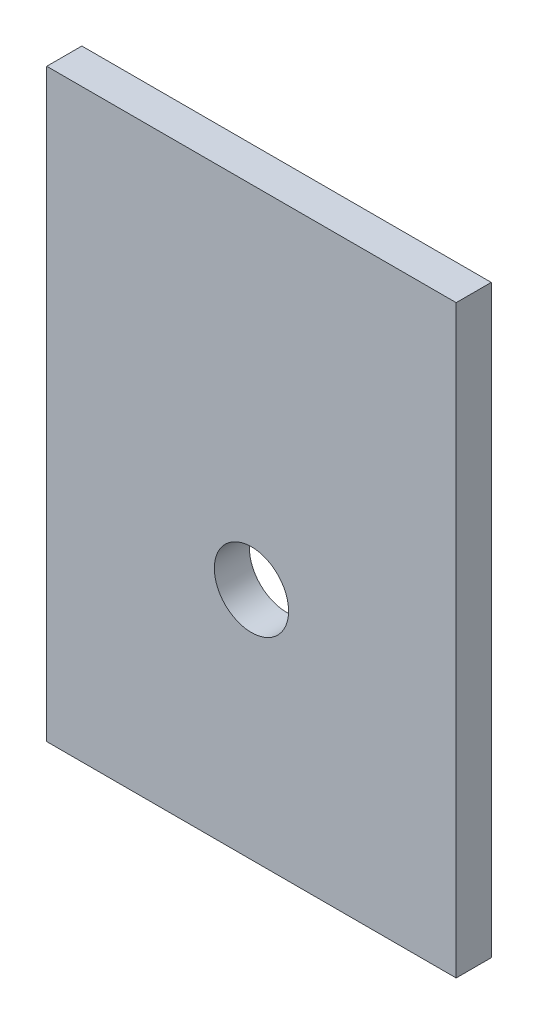
SolidWorks part; units mm, degrees
ref_plane "Front Plane" through (0, 0, 0) normal (0, 0, 1) x (1, 0, 0)
ref_plane "Top Plane" through (0, 0, 0) normal (0, 1, 0) x (1, 0, 0)
ref_plane "Right Plane" through (0, 0, 0) normal (1, 0, 0) x (0, 0, -1)
sketch "Sketch1" plane through (0, 0, 0) normal (0, 0, 1) x (1, 0, 0)
  line L1 (0, 0) -> (35, 0)
  line L2 (0, 0) -> (0, -50)
  line L3 (0, -50) -> (35, -50)
  line L4 (35, 0) -> (35, -50)
  dimension "D1" = 35
  dimension "D2" = 50
extrude "Boss-Extrude1" add sketch "Sketch1" along normal blind 3
sketch "Sketch2" plane through (0, 0, 3) normal (0, 0, 1) x (1, 0, 0)
  line L0 (0, -50) -> (35, -50) construction
  circle A0 centre (17.5, -30) radius 3.175
  point P4 (0, 0)
  point P5 (17.5, -50)
  dimension "D1" = 6.35
  dimension "D2" = 20
extrude "Cut-Extrude1" cut sketch "Sketch2" against normal through all
